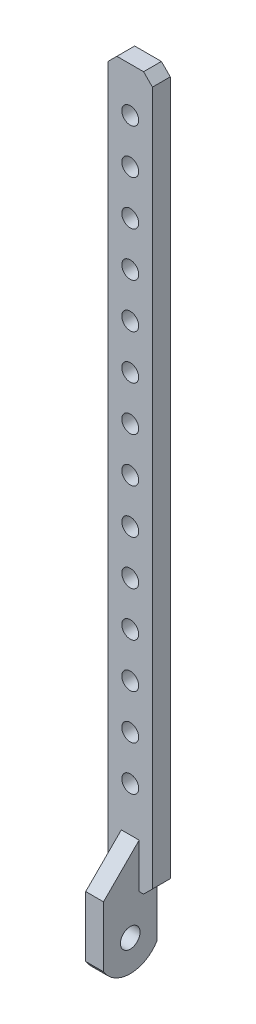
SolidWorks part; units mm, degrees
ref_plane "Front" through (0, 0, 0) normal (0, 0, 1) x (1, 0, 0)
ref_plane "Top" through (0, 0, 0) normal (0, 1, 0) x (1, 0, 0)
ref_plane "Right" through (0, 0, 0) normal (1, 0, 0) x (0, 0, -1)
sketch "Sketch1" plane through (0, 0, 0) normal (0, 0, 1) x (1, 0, 0)
  line L1 (-2.5, -40) -> (2.5, -40)
  line L2 (-2.5, -40) -> (-2.5, 40)
  line L3 (-2.5, 40) -> (2.5, 40)
  line L4 (2.5, -40) -> (2.5, 40)
  line L5 (-2.5, -40) -> (2.5, 40) construction
  line L6 (-2.5, 40) -> (2.5, -40) construction
  point P0 (0, 0)
  dimension "D1" = 5
  dimension "D2" = 80
extrude "Boss-Extrude1" add sketch "Sketch1" along normal blind 2
sketch "Sketch3" plane through (0, 0, 2) normal (0, 0, 1) x (1, 0, 0)
  line L0 (0, 40) -> (0, 35) construction
  line L1 (2.5, 40) -> (-2.5, 40) construction
  line L3 (0, 35) -> (0, 30) construction
  circle A0 centre (0, 35) radius 0.95
  circle A1 centre (0, 30) radius 0.95
  circle A2 centre (0, 25) radius 0.95
  circle A3 centre (0, 20) radius 0.95
  circle A4 centre (0, 15) radius 0.95
  circle A5 centre (0, 10) radius 0.95
  circle A6 centre (0, 5) radius 0.95
  circle A7 centre (0, 0) radius 0.95
  circle A8 centre (0, -5) radius 0.95
  circle A9 centre (0, -10) radius 0.95
  circle A10 centre (0, -15) radius 0.95
  circle A11 centre (0, -20) radius 0.95
  circle A12 centre (0, -25) radius 0.95
  circle A13 centre (0, -30) radius 0.95
  dimension "D1" = 1.9
  dimension "D2" = 5
  dimension "D4" = 5
  dimension "D3" = 14
extrude "Cut-Extrude1" cut sketch "Sketch3" against normal through all
sketch "Sketch2" plane through (0, 0, 0) normal (0, 0, -1) x (-1, 0, 0)
  line L0 (0, -40) -> (0, -44) construction
  line L1 (2.5, -40) -> (-2.5, -40) construction
  line L3 (-1, -48) -> (1, -48)
  line L4 (-1, -48) -> (-1, -40)
  line L5 (-1, -40) -> (1, -40)
  line L6 (1, -48) -> (1, -40)
  line L7 (-1, -48) -> (1, -40) construction
  line L8 (-1, -40) -> (1, -48) construction
  dimension "D1" = 8
  dimension "D2" = 2
extrude "Boss-Extrude2" add sketch "Sketch2" against normal blind 6
sketch "Sketch4" plane through (-1, 0, 0) normal (-1, 0, 0) x (0, 0, 1)
  line L0 (6, -40) -> (0, -48) construction
  line L1 (0, -48) -> (0, -40) construction
  line L2 (6, -48) -> (6, -40) construction
  line L3 (0, -45.8028) -> (0, -48)
  line L4 (0, -48) -> (6, -48)
  line L5 (6, -48) -> (6, -45.8028)
  circle A0 centre (3, -44) radius 1.1
  arc A1 (0, -45.8028) -> (6, -45.8028) centre (3, -44) ccw
  dimension "D1" = 2.2
  dimension "D2" = 3.5
extrude "Cut-Extrude2" cut sketch "Sketch4" against normal up to next
chamfer "Chamfer1" distance 5 angle 45 1 edges at (0, -40, 2)
chamfer "Chamfer2" distance 1 angle 45 4 edges at (-2.5, 40, 1) (2.5, 40, 1) (-2.5, -40, 1) (2.5, -40, 1)
